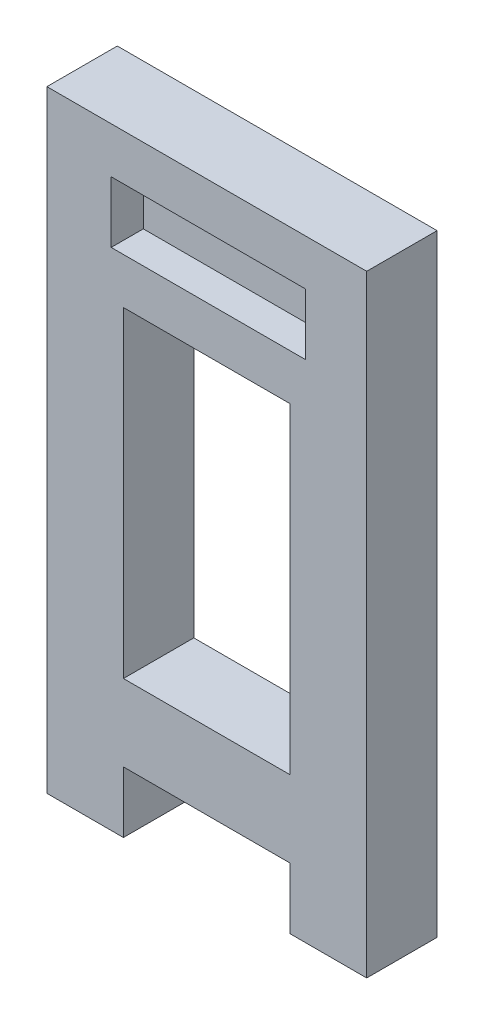
SolidWorks part; units mm, degrees
ref_plane "Front Plane" through (0, 0, 0) normal (0, 0, 1) x (1, 0, 0)
ref_plane "Top Plane" through (0, 0, 0) normal (0, 1, 0) x (1, 0, 0)
ref_plane "Right Plane" through (0, 0, 0) normal (1, 0, 0) x (0, 0, -1)
sketch "Sketch1" plane through (0, 0, 0) normal (0, 0, 1) x (1, 0, 0)
  line L0 (0, 0) -> (0, -2)
  line L1 (2.5, 0) -> (7.95, 0)
  line L2 (0, 0) -> (0, 18)
  line L3 (0, 18) -> (10.45, 18)
  line L4 (10.45, 0) -> (10.45, 18)
  line L5 (0, -2) -> (2.5, -2)
  line L6 (2.5, -2) -> (2.5, 0)
  line L7 (10.45, 0) -> (10.45, -2)
  line L8 (10.45, -2) -> (7.95, -2)
  line L9 (7.95, -2) -> (7.95, 0)
  line L12 (2.5, 2.5) -> (7.95, 2.5)
  line L13 (2.5, 2.5) -> (2.5, 13)
  line L14 (2.5, 13) -> (7.95, 13)
  line L15 (7.95, 2.5) -> (7.95, 13)
  line L16 (2.1, 14.5) -> (8.45, 14.5)
  line L17 (2.1, 14.5) -> (2.1, 16.5)
  line L18 (2.1, 16.5) -> (8.45, 16.5)
  line L19 (8.45, 14.5) -> (8.45, 16.5)
  point P19 (2.1, 15.5)
  dimension "D1" = 18
  dimension "D2" = 2
  dimension "D3" = 2.1
  dimension "D4" = 2
  dimension "D5" = 2
  dimension "D6" = 2.5
  dimension "D7" = 2.5
  dimension "D8" = 10.5
  dimension "D9" = 2
  dimension "D10" = 1.5
  dimension "D11" = 2.5
  dimension "D12" = 0.4
  dimension "D13" = 5.45
extrude "Boss-Extrude1" add sketch "Sketch1" along normal blind 2.3
extrude "Boss-Extrude2" add sketch "Sketch1<2>" along normal blind 1.25 contours L16 L19 L18 L17
sketch "Sketch1<2>" plane through (0, 0, 0) normal (0, 0, 1) x (1, 0, 0) same geometry as "Sketch1"
